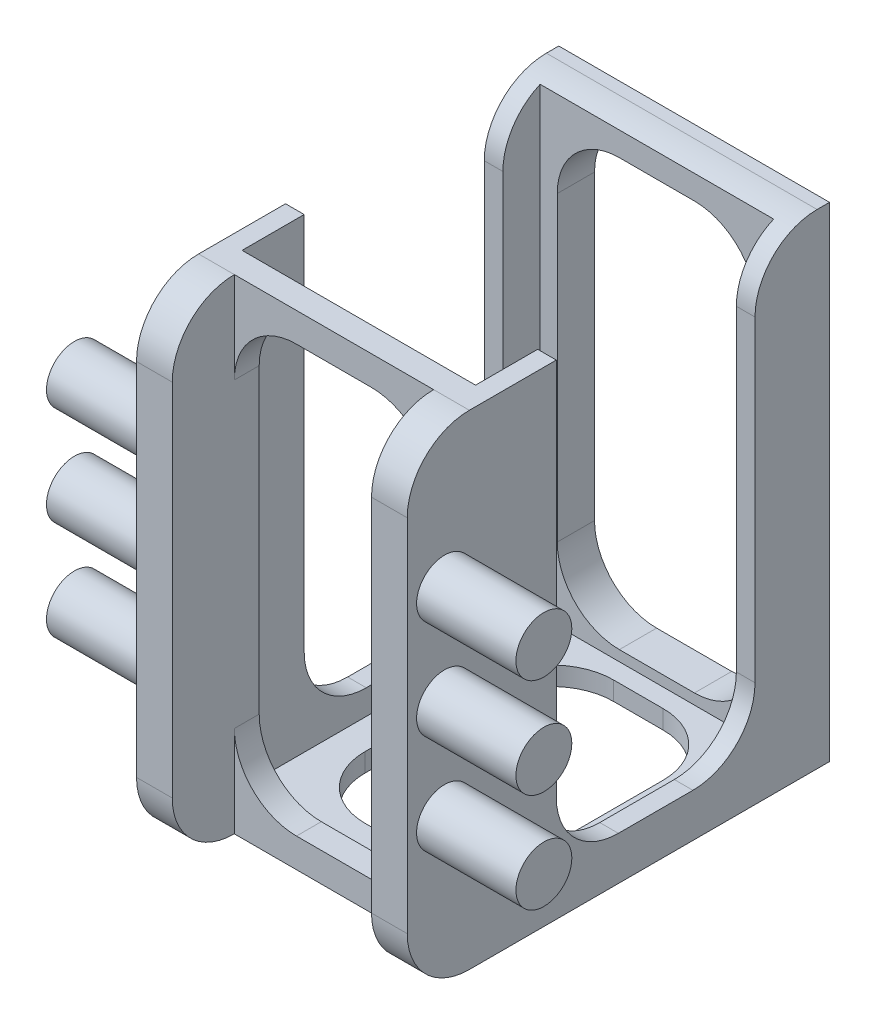
SolidWorks part; units mm, degrees
ref_plane "Front Plane" through (0, 0, 0) normal (0, 0, 1) x (1, 0, 0)
ref_plane "Top Plane" through (0, 0, 0) normal (0, 1, 0) x (1, 0, 0)
ref_plane "Right Plane" through (0, 0, 0) normal (1, 0, 0) x (0, 0, -1)
sketch "Sketch1" plane through (0, 0, 0) normal (0, 0, 1) x (1, 0, 0)
  line L1 (-10.9, -19.5) -> (10.9, -19.5)
  line L2 (-10.9, -19.5) -> (-10.9, 19.5)
  line L3 (-10.9, 19.5) -> (10.9, 19.5)
  line L4 (10.9, -19.5) -> (10.9, 19.5)
  line L5 (-10.9, -19.5) -> (10.9, 19.5) construction
  line L6 (-10.9, 19.5) -> (10.9, -19.5) construction
  point P0 (0, 0)
  dimension "D1" = 21.8
  dimension "D2" = 39
extrude "Boss-Extrude1" add sketch "Sketch1" along normal blind 3
sketch "Sketch2" plane through (0, 0, 3) normal (0, 0, 1) x (1, 0, 0)
  line L0 (-10.9, 19.5) -> (-9.4, 19.5)
  line L1 (10.9, 19.5) -> (-10.9, 19.5) construction
  line L2 (-9.4, 19.5) -> (-9.4, -18)
  line L3 (-9.4, -18) -> (9.4, -18)
  line L4 (9.4, -18) -> (9.4, 19.5)
  line L5 (9.4, 19.5) -> (10.9, 19.5)
  line L6 (10.9, 19.5) -> (10.9, -19.5)
  line L7 (10.9, -19.5) -> (-10.9, -19.5)
  line L8 (-10.9, -19.5) -> (-10.9, 19.5)
  line L9 (-9.4, -18) -> (-9.4, -19.5) construction
  dimension "D1" = 1.5
  dimension "D2" = 1.5
  dimension "D3" = 1.5
extrude "Boss-Extrude2" add sketch "Sketch2" along normal blind 3 contours L8 L0 L2 L3 L4 L5 L6 L7
sketch "Sketch3" plane through (0, 0, 6) normal (0, 0, 1) x (1, 0, 0)
  line L5 (-9.4, -18) -> (-10.9, -18)
  line L6 (-10.9, -19.5) -> (-10.9, 19.5) construction
  line L7 (-10.9, -18) -> (-10.9, -19.5)
  line L8 (-10.9, -19.5) -> (10.9, -19.5)
  line L9 (10.9, -19.5) -> (10.9, -18)
  line L10 (10.9, 19.5) -> (10.9, -19.5) construction
  line L11 (10.9, -18) -> (-9.4, -18)
extrude "Boss-Extrude4" add sketch "Sketch3" along normal blind 21 contours L11 L5 L7 L8 L9
sketch "Sketch4" plane through (0, 0, 27) normal (0, 0, 1) x (1, 0, 0)
  line L1 (-10.9, -19.5) -> (10.9, -19.5)
  line L2 (-10.9, -19.5) -> (-10.9, 19.5)
  line L3 (-10.9, 19.5) -> (10.9, 19.5)
  line L4 (10.9, -19.5) -> (10.9, 19.5)
  dimension "D1" = 21.8
extrude "Boss-Extrude5" add sketch "Sketch4" along normal blind 2
sketch "Sketch5" plane through (0, -19.5, 0) normal (0, -1, 0) x (1, 0, 0)
  line L0 (-10.9, 29) -> (10.9, 0) construction
  line L1 (10.9, 29) -> (-10.9, 0) construction
  line L3 (-7, 4.5) -> (7, 4.5)
  line L4 (-7, 4.5) -> (-7, 24.5)
  line L5 (-7, 24.5) -> (7, 24.5)
  line L6 (7, 4.5) -> (7, 24.5)
  line L7 (-7, 4.5) -> (7, 24.5) construction
  line L8 (-7, 24.5) -> (7, 4.5) construction
  point P8 (0, 14.5)
  dimension "D1" = 14
  dimension "D2" = 20
extrude "Cut-Extrude1" cut sketch "Sketch5" against normal through all and the other way through all
sketch "Sketch6" plane through (0, 0, 27) normal (0, 0, -1) x (-1, 0, 0)
  line L0 (-9.4, -18) -> (-9.4, 18)
  line L1 (-10.9, -18) -> (10.9, -18) construction
  line L2 (-9.4, 18) -> (9.4, 18)
  line L3 (9.4, 18) -> (9.4, -18)
  line L4 (-9.4, -18) -> (-10.9, -18)
  line L5 (-10.9, -18) -> (-10.9, 19.5)
  line L6 (-10.9, 19.5) -> (10.9, 19.5)
  line L7 (10.9, 19.5) -> (10.9, -18)
  line L8 (10.9, -18) -> (9.4, -18)
  line L9 (-1.4901, 18) -> (-1.4901, 19.5) construction
  dimension "D1" = 1.5
  dimension "D2" = 1.5
  dimension "D3" = 1.5
extrude "Boss-Extrude6" add sketch "Sketch6" along normal blind 5
sketch "Sketch7" plane through (0, 0, 22) normal (0, 0, -1) x (-1, 0, 0)
  line L0 (10.9, 19.5) -> (-10.9, 19.5) construction
  line L10 (-7.3, 18) -> (7.3, 18)
  line L11 (-7.3, 18) -> (-7.3, 19.5)
  line L12 (-7.3, 19.5) -> (7.3, 19.5)
  line L13 (7.3, 18) -> (7.3, 19.5)
  line L14 (-7.3, 18) -> (7.3, 18)
  line L15 (-7.3, 18) -> (-7.3, 19.5)
  line L16 (-7.3, 19.5) -> (7.3, 19.5)
  line L17 (7.3, 18) -> (7.3, 19.5)
extrude "Cut-Extrude2" cut sketch "Sketch7" against normal blind 2 contours L11 L10 L13 L12
sketch "Sketch8" plane through (0, 0, 3) normal (0, 0, 1) x (1, 0, 0)
  line L1 (-8.0221, -17.151) -> (8.0221, -17.151)
  line L2 (-8.0221, -17.151) -> (-8.0221, 17.151)
  line L3 (-8.0221, 17.151) -> (8.0221, 17.151)
  line L4 (8.0221, -17.151) -> (8.0221, 17.151)
  line L5 (-8.0221, -17.151) -> (8.0221, 17.151) construction
  line L6 (-8.0221, 17.151) -> (8.0221, -17.151) construction
  point P0 (0, 0)
extrude "Cut-Extrude3" cut sketch "Sketch8" against normal through all
sketch "Sketch9" plane through (0, 0, 27) normal (0, 0, -1) x (-1, 0, 0)
  line L1 (-8.0221, -17.151) -> (8.0221, -17.151)
  line L2 (-8.0221, -17.151) -> (-8.0221, 17.151)
  line L3 (-8.0221, 17.151) -> (8.0221, 17.151)
  line L4 (8.0221, -17.151) -> (8.0221, 17.151)
  line L5 (-8.0221, -17.151) -> (8.0221, 17.151) construction
  line L6 (-8.0221, 17.151) -> (8.0221, -17.151) construction
  point P0 (0, 0)
extrude "Cut-Extrude4" cut sketch "Sketch9" against normal blind 2
sketch "Sketch10" plane through (0, 0, 22) normal (0, 0, -1) x (-1, 0, 0)
  line L1 (9.4, 18) -> (7.3, 18)
  line L2 (9.4, 18) -> (9.4, 19.5)
  line L3 (9.4, 19.5) -> (7.3, 19.5)
  line L4 (7.3, 18) -> (7.3, 19.5)
extrude "Cut-Extrude5" cut sketch "Sketch10" against normal blind 2
sketch "Sketch11" plane through (0, 0, 22) normal (0, 0, -1) x (-1, 0, 0)
  line L1 (-9.4, 18) -> (-7.3, 18)
  line L2 (-9.4, 18) -> (-9.4, 19.5)
  line L3 (-9.4, 19.5) -> (-7.3, 19.5)
  line L4 (-7.3, 18) -> (-7.3, 19.5)
extrude "Cut-Extrude6" cut sketch "Sketch11" against normal blind 2
sketch "Sketch13" plane through (0, 0, 24) normal (0, 0, -1) x (-1, 0, 0)
  line L1 (-9.4, 18) -> (9.4, 18)
  line L2 (-9.4, 18) -> (-9.4, 19.5)
  line L3 (-9.4, 19.5) -> (9.4, 19.5)
  line L4 (9.4, 18) -> (9.4, 19.5)
extrude "Cut-Extrude7" cut sketch "Sketch13" against normal blind 3
sketch "Sketch16" plane through (-10.9, 0, 0) normal (-1, 0, 0) x (0, 0, 1)
  line L0 (22, 8.15) -> (23.15, 8.15) construction
  line L1 (25.5, 19.5) -> (25.5, 10.5) construction
  line L3 (29, 19.5) -> (22, 19.5) construction
  line L4 (22, -18) -> (22, 19.5) construction
  dimension "D3" = 1.15
fillet "Fillet3" radius 5 6 edges at (-8.0221, -17.151, 28) (8.0221, -17.151, 28) (-8.0221, 17.151, 1.5) (8.0221, 17.151, 1.5) (-8.0221, -17.151, 1.5) (8.0221, -17.151, 1.5)
fillet "Fillet4" radius 5 2 edges at (-8.0221, 17.151, 28) (8.0221, 17.151, 28)
sketch "Sketch17" plane through (0, -18, 0) normal (0, 1, 0) x (1, 0, 0)
  line L0 (-10.9, -6) -> (-9.4, -6)
  line L1 (-9.4, -6) -> (-9.4, -22)
  line L2 (-9.4, -22) -> (-10.9, -22)
  line L3 (-10.9, -22) -> (-10.9, -6)
  line L4 (9.4, -6) -> (9.4, -22)
  line L5 (9.4, -22) -> (10.9, -22)
  line L6 (10.9, -22) -> (10.9, -6)
  line L7 (10.9, -6) -> (9.4, -6)
extrude "Boss-Extrude8" add sketch "Sketch17" along normal blind 2
fillet "Fillet5" radius 5 8 edges at (7, -18.75, 24.5) (7, -18.75, 4.5) (-7, -18.75, 24.5) (-7, -18.75, 4.5) (-10.15, -16, 22) (10.15, -16, 22) (-10.15, -16, 6) (10.15, -16, 6)
sketch "Sketch19" plane through (0, 0, 29) normal (0, 0, 1) x (1, 0, 0)
  line L0 (-10.9, 19.5) -> (-10.9, -19.5)
  line L2 (-10.9, -19.5) -> (10.9, -19.5) construction
  line L4 (-8.0221, -12.151) -> (-8.0221, 12.151)
  line L5 (-8.0221, 12.151) -> (-8.0221, 19.5)
  line L6 (10.9, 19.5) -> (-10.9, 19.5) construction
  line L7 (-8.0221, 19.5) -> (-10.9, 19.5)
  line L8 (-8.0221, -12.151) -> (-8.0221, -19.5)
  line L9 (8.0221, 12.151) -> (8.0221, 19.5)
  line L10 (8.0221, 19.5) -> (10.9, 19.5)
  line L11 (10.9, 19.5) -> (10.9, -19.5)
  line L12 (10.9, -19.5) -> (8.0221, -19.5)
  line L13 (8.0221, -19.5) -> (8.0221, 12.151)
  line L14 (-10.9, -19.5) -> (-8.0221, -19.5)
extrude "Boss-Extrude9" add sketch "Sketch19" along normal blind 5
sketch "Sketch24" plane through (-10.9, 0, 0) normal (-1, 0, 0) x (0, 0, 1)
  line L0 (22, 8.15) -> (31, 8.15) construction
  circle A0 centre (31, 8.15) radius 2.25
  circle A1 centre (31, 0.15) radius 2.25
  circle A2 centre (31, -7.85) radius 2.25
  dimension "D2" = 4.5
  dimension "D1" = 9
  dimension "D3" = 3
extrude "Boss-Extrude10" add sketch "Sketch24" along normal blind 8
sketch "Sketch25" plane through (10.9, 0, 0) normal (1, 0, 0) x (0, 0, -1)
  line L0 (-22, 8.15) -> (-31, 8.15) construction
  line L1 (-31, -7.85) -> (-31, -19.5) construction
  line L2 (-34, -19.5) -> (0, -19.5) construction
  circle A0 centre (-31, 8.15) radius 2.25
  circle A1 centre (-31, 0.15) radius 2.25
  circle A2 centre (-31, -7.85) radius 2.25
  dimension "D2" = 4.5
  dimension "D1" = 9
  dimension "D4" = 11.65
  dimension "D3" = 3
extrude "Boss-Extrude11" add sketch "Sketch25" along normal blind 8
fillet "Fillet7" radius 5 5 edges at (-9.4611, -19.5, 34) (9.4611, -19.5, 34) (-10.15, 19.5, 6) (9.4611, 19.5, 34) (-9.4611, 19.5, 34)
